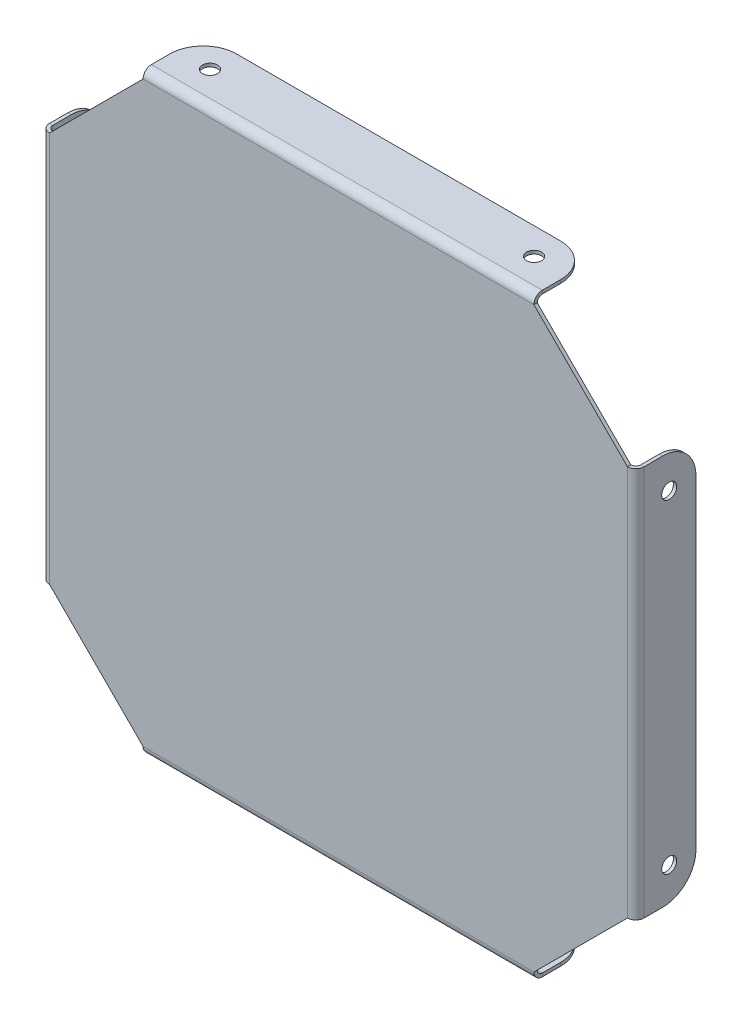
SolidWorks part; units mm, degrees
note: The reader was unsure of these and kept them because the rebuilt part matched: flange length of "Hori Edge", "Vert Edge".
material "1060-O (SS)"
ref_plane "Front Plane" through (0, 0, 0) normal (0, 0, 1) x (1, 0, 0)
ref_plane "Top Plane" through (0, 0, 0) normal (0, 1, 0) x (1, 0, 0)
ref_plane "Right Plane" through (0, 0, 0) normal (1, 0, 0) x (0, 0, -1)
sketch "Sketch1" plane through (0, 0, 0) normal (0, 0, 1) x (1, 0, 0)
  line L0 (-86.5, -58.5) -> (-58.5, -86.5)
  line L1 (-58.5, -86.5) -> (58.5, -86.5)
  line L2 (-86.5, -58.5) -> (-86.5, 58.5)
  line L3 (-58.5, 86.5) -> (58.5, 86.5)
  line L4 (86.5, -58.5) -> (86.5, 58.5)
  line L5 (-86.5, -86.5) -> (86.5, 86.5) construction
  line L6 (-86.5, 86.5) -> (86.5, -86.5) construction
  line L7 (58.5, -86.5) -> (86.5, -58.5)
  line L8 (58.5, 86.5) -> (86.5, 58.5)
  line L9 (-86.5, 58.5) -> (-58.5, 86.5)
  point P0 (0, 0)
  dimension "D1" = 173
  dimension "D2" = 173
base flange "Main Plate" sketch "Sketch1" thickness 1 reverse thickness direction no parameters "D1"=1.5
edge flange "Hori Edge" sketch "Sketch9" flange angle 90 flange length 18 flange position bend outside bend radius 1.5 thickness 1 relief obround parameters "D6"=10
sketch "Sketch9" plane through (0, 86.5, -1) normal (0, 1, 0) x (1, 0, 0)
  line L2 (-58.5, 0) -> (-58.5, 17)
  line L3 (-58.5, 17) -> (58.5, 17)
  line L4 (58.5, 17) -> (58.5, 0)
  line L5 (58.5, 0) -> (-58.5, 0) construction
  line L6 (58.5, 0) -> (-58.5, 0)
bend "EdgeBend1" bend radius 1.5 bend angle 90 parameters "D5"=1
fillet "Hori Edge Fillets" radius 10 2 edges at (-58.5, 88.5, -18) (58.5, 88.5, -18)
hole_wizard "M4 Clearance Hole1" positions "Sketch13" profile "Sketch14" hole size "M4" standard "ISO" end condition up to next
sketch "Sketch13" plane through (0, 89, 0) normal (0, 1, 0) x (1, 0, 0)
  line L0 (58.5, 0) -> (-58.5, 0) construction
  point P0 (-48.5, 10.0429)
  point P2 (48.5, 10.0429)
  dimension "D1" = 10.0429
sketch "Sketch14" plane through (-48.5, 89, -10.0429) normal (1, 0, 0) x (0, 0, 1)
  line L0 (0, 0) -> (0, 178)
  line L1 (0, 178) -> (2.25, 178)
  line L2 (2.25, 178) -> (2.25, 0)
  line L5 (2.25, 0) -> (0, 0)
  line L11 (0, -6.35) -> (0, 107.95) construction
  dimension "Thru Hole Dia." = 4.5
  dimension "Thru Hole Depth" = 178
edge flange "Vert Edge" sketch "Sketch12" flange angle 90 flange length 18 flange position bend outside bend radius 1.5 thickness 1 relief obround parameters "D6"=10
sketch "Sketch12" plane through (86.5, 0, -1) normal (1, 0, 0) x (0, -1, 0)
  line L2 (-58.5, 0) -> (-58.5, 17)
  line L3 (-58.5, 17) -> (58.5, 17)
  line L4 (58.5, 17) -> (58.5, 0)
  line L5 (58.5, 0) -> (-58.5, 0) construction
  line L6 (58.5, 0) -> (-58.5, 0)
bend "EdgeBend2" bend radius 1.5 bend angle 90 parameters "D5"=3
fillet "Vert Edge Fillets" radius 10 2 edges at (88.5, -58.5, -18) (88.5, 58.5, -18)
hole_wizard "M4 Clearance Hole2" positions "Sketch15" profile "Sketch16" hole size "M4" standard "ISO" end condition up to next
sketch "Sketch15" plane through (89, 0, 0) normal (1, 0, 0) x (0, 0, -1)
  line L0 (0, -58.5) -> (0, 58.5) construction
  point P0 (10, 48.5)
  point P2 (10, -48.5)
  dimension "D1" = 10
sketch "Sketch16" plane through (89, 48.5, -10) normal (0, 1, 0) x (0, 0, -1)
  line L0 (0, 0) -> (0, 178)
  line L1 (0, 178) -> (2.25, 178)
  line L2 (2.25, 178) -> (2.25, 0)
  line L5 (2.25, 0) -> (0, 0)
  line L11 (0, -6.35) -> (0, 107.95) construction
  dimension "Thru Hole Dia." = 4.5
  dimension "Thru Hole Depth" = 178
mirror "Other Hori Edge" about plane through (0, 0, 0) normal (0, 1, 0) of "M4 Clearance Hole1", "Hori Edge", "Hori Edge Fillets"
bend "MirrorBend1" bend radius 1.5 bend angle 90 parameters "D5"=2
mirror "Other Vert Edge" about plane through (0, 0, 0) normal (1, 0, 0) of "M4 Clearance Hole2", "Vert Edge", "Vert Edge Fillets"
bend "MirrorBend2" bend radius 1.5 bend angle 90 parameters "D5"=4
sketch "Bend-Lines1" [suppressed] plane through (0, 0, 0) normal (0, 1, 0) x (1, 0, 0)
sketch "Bounding-Box1" [suppressed] plane through (0, 0, 0) normal (0, 1, 0) x (1, 0, 0)
sheet metal parameters "Sheet-Metal1" thickness 1 parameters "D1"=1.5
flat pattern "Flat-Pattern1" [suppressed]
sketch "Bend-Lines2" plane through (0, 0, 0) normal (0, 1, 0) x (1, 0, 0)
sketch3d "Bounding-Box2" [suppressed]
  line L0 (-126.5, -86.5, 0) -> (126.5, -86.5, 0) construction
  line L1 (-126.5, 86.5, 0) -> (126.5, 86.5, 0) construction
  line L2 (-126.5, -86.5, 0) -> (-126.5, 86.5, 0) construction
  line L3 (126.5, -86.5, 0) -> (126.5, 86.5, 0) construction
sheet metal parameters "Sheet-Metal2" thickness 1 parameters "D1"=1.5
flat pattern "Flat-Pattern1"
sketch "Bend-Lines2" plane through (0, 0, 0) normal (0, 0, 1) x (1, 0, 0)
  line L0 (58.5, 88.0708) -> (-58.5, 88.0708) construction
  line L1 (58.5, 88.0708) -> (-58.5, 88.0708) construction
sketch3d "Bounding-Box2" [suppressed]
  line L0 (86.5, 105.1416, 0) -> (86.5, -86.5, 0) construction
  line L1 (-86.5, 105.1416, 0) -> (-86.5, -86.5, 0) construction
  line L2 (86.5, 105.1416, 0) -> (-86.5, 105.1416, 0) construction
  line L3 (86.5, -86.5, 0) -> (-86.5, -86.5, 0) construction
bend of the flat pattern "Flatten-<EdgeBend1>1"
sheet metal parameters "Sheet-Metal3" thickness 1 parameters "D1"=1.5
flat pattern "Flat-Pattern1" [suppressed]
sketch "Bend-Lines2" plane through (0, 0, 0) normal (0, 0, 1) x (1, 0, 0)
  line L0 (98.5, 88.0708) -> (-98.5, 88.0708) construction
  line L1 (98.5, 88.0708) -> (-98.5, 88.0708) construction
  line L2 (-98.5, -88.0708) -> (98.5, -88.0708) construction
  line L3 (-98.5, -88.0708) -> (98.5, -88.0708) construction
sketch3d "Bounding-Box2" [suppressed]
  line L0 (-126.5, -104.1416, 0) -> (126.5, -104.1416, 0) construction
  line L1 (-126.5, 104.1416, 0) -> (126.5, 104.1416, 0) construction
  line L2 (-126.5, -104.1416, 0) -> (-126.5, 104.1416, 0) construction
  line L3 (126.5, -104.1416, 0) -> (126.5, 104.1416, 0) construction
bend of the flat pattern "Flatten-<EdgeBend1>1"
bend of the flat pattern "Flatten-<MirrorBend1>1"
bend of the flat pattern "Flatten-<EdgeBend2>2"
sheet metal parameters "Sheet-Metal4" thickness 1 parameters "D1"=1.5
flat pattern "Flat-Pattern1"
sketch "Bend-Lines2" plane through (0, 0, 0) normal (0, 0, 1) x (1, 0, 0)
  line L0 (58.5, 88.0708) -> (-58.5, 88.0708) construction
  line L1 (58.5, 88.0708) -> (-58.5, 88.0708) construction
  line L4 (88.0708, -58.5) -> (88.0708, 58.5) construction
  line L5 (88.0708, -58.5) -> (88.0708, 58.5) construction
sketch3d "Bounding-Box2" [suppressed]
  line L0 (-86.5, -86.5, 0) -> (105.1416, -86.5, 0) construction
  line L1 (-86.5, 105.1416, 0) -> (105.1416, 105.1416, 0) construction
  line L2 (-86.5, -86.5, 0) -> (-86.5, 105.1416, 0) construction
  line L3 (105.1416, -86.5, 0) -> (105.1416, 105.1416, 0) construction
bend of the flat pattern "Flatten-<EdgeBend1>1"
bend of the flat pattern "Flatten-<EdgeBend2>1"
sheet metal parameters "Sheet-Metal5" thickness 1 parameters "D1"=1.5
flat pattern "Flat-Pattern1"
sketch "Bend-Lines2" plane through (0, 0, 0) normal (0, 0, 1) x (1, 0, 0)
  line L0 (58.5, 88.0708) -> (-58.5, 88.0708) construction
  line L1 (58.5, 88.0708) -> (-58.5, 88.0708) construction
  line L2 (-58.5, -88.0708) -> (58.5, -88.0708) construction
  line L3 (-58.5, -88.0708) -> (58.5, -88.0708) construction
  line L4 (88.0708, -58.5) -> (88.0708, 58.5) construction
  line L5 (88.0708, -58.5) -> (88.0708, 58.5) construction
  line L6 (-88.0708, 58.5) -> (-88.0708, -58.5) construction
  line L7 (-88.0708, 58.5) -> (-88.0708, -58.5) construction
sketch3d "Bounding-Box2" [suppressed]
  line L0 (-105.1416, -105.1416, 0) -> (105.1416, -105.1416, 0) construction
  line L1 (-105.1416, 105.1416, 0) -> (105.1416, 105.1416, 0) construction
  line L2 (-105.1416, -105.1416, 0) -> (-105.1416, 105.1416, 0) construction
  line L3 (105.1416, -105.1416, 0) -> (105.1416, 105.1416, 0) construction
bend of the flat pattern "Flatten-<EdgeBend1>1"
bend of the flat pattern "Flatten-<MirrorBend1>1"
bend of the flat pattern "Flatten-<EdgeBend2>1"
bend of the flat pattern "Flatten-<MirrorBend2>1"
sheet metal parameters "Sheet-Metal6" thickness 1 parameters "D1"=1.5
flat pattern "Flat-Pattern1" [suppressed]
sketch "Bend-Lines2" plane through (0, 0, 0) normal (0, 0, 1) x (1, 0, 0)
  line L0 (58.5, 88.0708) -> (-58.5, 88.0708) construction
  line L1 (58.5, 88.0708) -> (-58.5, 88.0708) construction
sketch3d "Bounding-Box2" [suppressed]
  line L0 (86.5, 105.1416, 0) -> (86.5, -86.5, 0) construction
  line L1 (-86.5, 105.1416, 0) -> (-86.5, -86.5, 0) construction
  line L2 (86.5, 105.1416, 0) -> (-86.5, 105.1416, 0) construction
  line L3 (86.5, -86.5, 0) -> (-86.5, -86.5, 0) construction
bend of the flat pattern "Flatten-<EdgeBend1>1"
bend of the flat pattern "Flatten-<MirrorBend2>2"
bend of the flat pattern "Flatten-<MirrorBend1>2"
sheet metal parameters "Sheet-Metal7" thickness 1 parameters "D1"=1.5
flat pattern "Flat-Pattern1"
sketch "Bend-Lines2" plane through (0, 0, 0) normal (0, 0, 1) x (1, 0, 0)
  line L0 (58.5, 88.0708) -> (-58.5, 88.0708) construction
  line L1 (58.5, 88.0708) -> (-58.5, 88.0708) construction
  line L4 (88.0708, -58.5) -> (88.0708, 58.5) construction
  line L5 (88.0708, -58.5) -> (88.0708, 58.5) construction
sketch3d "Bounding-Box2" [suppressed]
  line L0 (-86.5, -86.5, 0) -> (105.1416, -86.5, 0) construction
  line L1 (-86.5, 105.1416, 0) -> (105.1416, 105.1416, 0) construction
  line L2 (-86.5, -86.5, 0) -> (-86.5, 105.1416, 0) construction
  line L3 (105.1416, -86.5, 0) -> (105.1416, 105.1416, 0) construction
bend of the flat pattern "Flatten-<EdgeBend1>1"
bend of the flat pattern "Flatten-<EdgeBend2>1"
